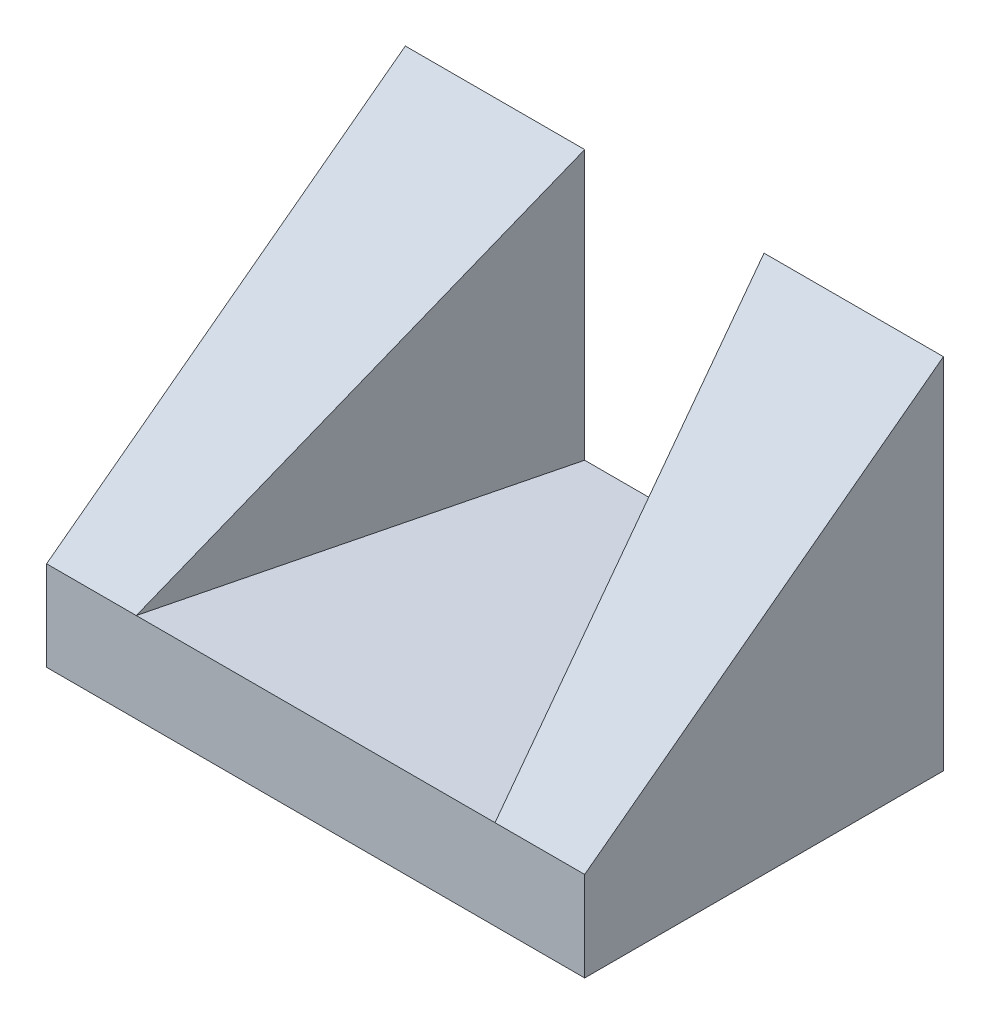
SolidWorks part; units mm, degrees
ref_plane "Front Plane" through (0, 0, 0) normal (0, 0, 1) x (1, 0, 0)
ref_plane "Top Plane" through (0, 0, 0) normal (0, 1, 0) x (1, 0, 0)
ref_plane "Right Plane" through (0, 0, 0) normal (1, 0, 0) x (0, 0, -1)
sketch "Sketch1" plane through (0, 0, 0) normal (0, 1, 0) x (1, 0, 0)
  line L0 (0, 0) -> (0, 40000)
  line L1 (0, 40000) -> (60000, 40000)
  line L2 (60000, 40000) -> (60000, 0)
  line L3 (60000, 0) -> (0, 0)
  line L4 (10000, 0) -> (20000, 40000)
  line L5 (20000, 40000) -> (40000, 40000)
  line L6 (30000, 40000) -> (30000, 0) construction
  line L7 (40000, 40000) -> (50000, 0)
  dimension "D1" = 60000
  dimension "D2" = 40000
  dimension "D3" = 40000
  dimension "D4" = 20000
  dimension "D5" = 10000
  dimension "D6" = 20000
extrude "Boss-Extrude1" add sketch "Sketch1" along normal blind 10000 contours L5 L6 L3 L7 | L6 L1 L4 L3 region at (22222.2222, 0, -17777.7778) region at (37777.7778, 0, -17777.7778)
extrude "Boss-Extrude2" add sketch "Sketch1<3>" along normal blind 40000 contours L1 L7 L3 L2 | L3 L4 L1 L0 region at (7777.7778, 0, -22222.2222) region at (52222.2222, 0, -22222.2222)
sketch "Sketch1<3>" plane through (0, 0, 0) normal (0, 1, 0) x (1, 0, 0) same geometry as "Sketch1"
sketch "Sketch2" plane through (0, 0, 0) normal (0, 0, 1) x (1, 0, 0)
  line L1 (60000, 40000) -> (60000, 0) construction
  line L2 (60000, 10000) -> (60000, 40000)
sketch "Sketch3" plane through (60000, 0, 0) normal (1, 0, 0) x (0, 0, -1)
  line L0 (40000, 40000) -> (0, 10000)
  line L1 (0, 10000) -> (0, 40000) construction
  line L2 (0, 40000) -> (0, 0) construction
  dimension "D1" = 10000
extrude "Cut-Extrude1" cut sketch "Sketch3" against normal through all and the other way through all flip side to cut contours L0
